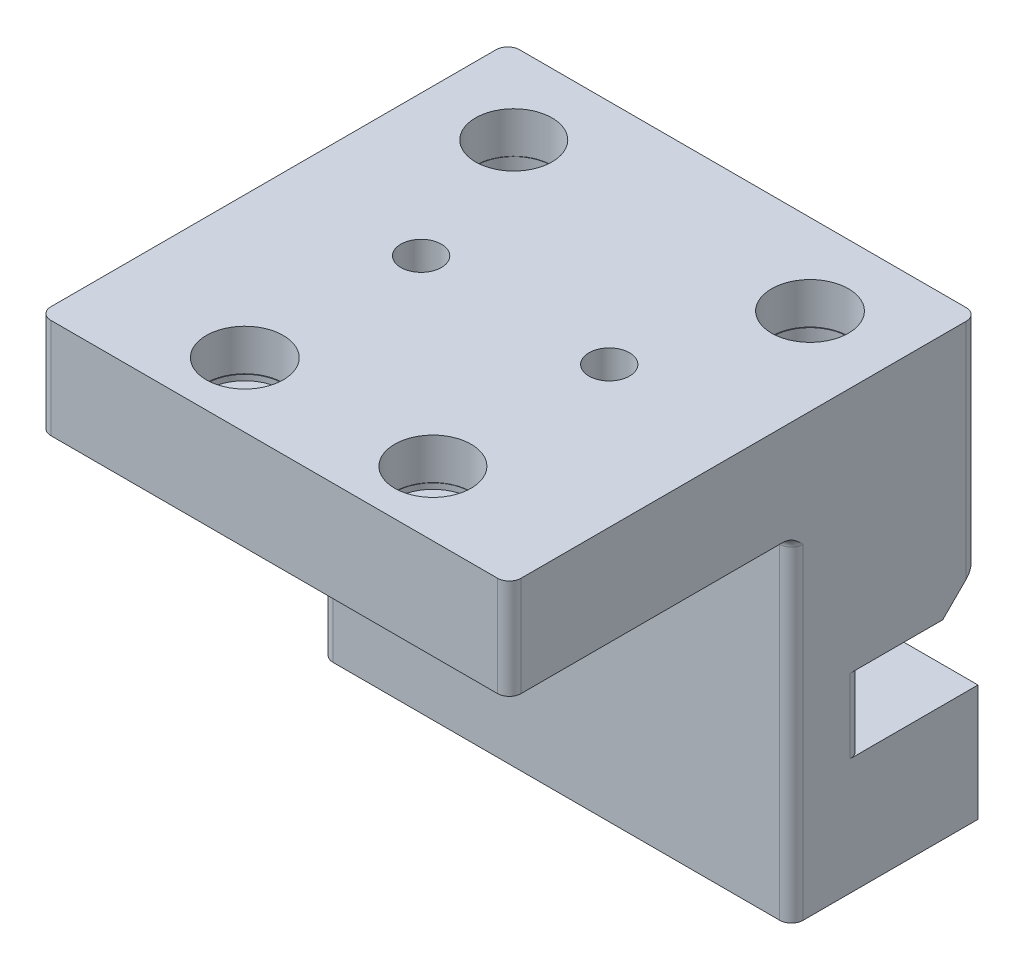
SolidWorks part; units mm, degrees
ref_plane "Front Plane" through (0, 0, 0) normal (0, 0, 1) x (1, 0, 0)
ref_plane "Top Plane" through (0, 0, 0) normal (0, 1, 0) x (1, 0, 0)
ref_plane "Right Plane" through (0, 0, 0) normal (1, 0, 0) x (0, 0, -1)
sketch "Sketch1" plane through (0, 0, 0) normal (0, 1, 0) x (1, 0, 0)
  line L1 (20, 11) -> (-20, 11)
  line L2 (20, 11) -> (20, -11)
  line L3 (20, -11) -> (-20, -11)
  line L4 (-20, 11) -> (-20, -11)
  line L5 (20, 11) -> (-20, -11) construction
  line L6 (20, -11) -> (-20, 11) construction
  point P0 (0, 0)
  dimension "D1" = 22
  dimension "D2" = 40
extrude "Boss-Extrude1" add sketch "Sketch1" along normal blind 5
sketch "Sketch2" plane through (0, 5, 0) normal (0, 1, 0) x (1, 0, 0)
  line L1 (8, 7.5) -> (-8, 7.5)
  line L2 (8, 7.5) -> (8, -7.5)
  line L3 (8, -7.5) -> (-8, -7.5)
  line L4 (-8, 7.5) -> (-8, -7.5)
  line L5 (8, 7.5) -> (-8, -7.5) construction
  line L6 (8, -7.5) -> (-8, 7.5) construction
  point P0 (0, 0)
  dimension "D1" = 15
  dimension "D2" = 16
hole_wizard "CBORE for M3 SHCS1" positions "Sketch5" profile "Sketch4" counterbore size "M3" standard "ANSI Metric" end condition through all
sketch "Sketch5" plane through (0, 5, 0) normal (0, 1, 0) x (1, 0, 0)
  point P6 (8, -7.5)
  point P9 (-8, -7.5)
sketch "Sketch4" plane through (8, 5, 7.5) normal (1, 0, 0) x (0, 0, 1)
  line L0 (0, 0) -> (0, 5)
  line L1 (0, 5) -> (1.7, 5)
  line L3 (1.7, 5) -> (1.7, 3)
  line L4 (3.25, 3) -> (1.7, 3)
  line L5 (3.25, 3) -> (3.25, 0.025)
  line L6 (3.25, 0.025) -> (3.275, 0)
  line L7 (3.275, 0) -> (0, 0)
  line L8 (-3.25, 0.025) -> (-3.275, 0) construction
  line L11 (0, -6.35) -> (0, 107.95) construction
  dimension "Thru Hole Dia." = 3.4
  dimension "Thru Hole Depth" = 5
  dimension "C'Bore Dia." = 6.5
  dimension "C'Bore Depth" = 3
  dimension "Near C'Sink Dia." = 6.55
  dimension "Near C'Sink Angle" = 90
sketch "Sketch6" plane through (0, 5, 0) normal (0, 1, 0) x (1, 0, 0)
  line L0 (20, -11) -> (20, 11) construction
  line L1 (-20, 11) -> (20, 11)
  line L2 (-20, 11) -> (-20, 17)
  line L3 (-20, 17) -> (20, 17)
  line L4 (20, 11) -> (20, 17)
  dimension "D1" = 6
extrude "Boss-Extrude2" add sketch "Sketch6" against normal blind 28.7
sketch "Sketch7" plane through (0, 0, -17) normal (0, 0, -1) x (-1, 0, 0)
  line L0 (20, -23.7) -> (20, 5) construction
  line L1 (-20, -23.7) -> (20, -23.7)
  line L2 (-20, -23.7) -> (-20, -18.8)
  line L3 (-20, -18.8) -> (20, -18.8)
  line L4 (20, -23.7) -> (20, -18.8)
  dimension "D1" = 4.9
extrude "Boss-Extrude3" add sketch "Sketch7" along normal blind 9.87
sketch "Sketch8" plane through (0, 0, -17) normal (0, 0, -1) x (-1, 0, 0)
  line L0 (20, -18.8) -> (20, 5) construction
  line L1 (-20, 5) -> (20, 5)
  line L2 (-20, 5) -> (-20, -12.5)
  line L3 (-20, -12.5) -> (20, -12.5)
  line L4 (20, 5) -> (20, -12.5)
  dimension "D1" = 17.5
extrude "Boss-Extrude4" add sketch "Sketch8" along normal up to surface (9.87 mm away) up to face at (0, -21.25, -26.87)
sketch "Sketch18" plane through (0, 0, 11) normal (0, 0, 1) x (1, 0, 0)
  line L4 (-20, 0) -> (20, 0)
  line L5 (20, 0) -> (20, 5)
  line L6 (20, 5) -> (-20, 5)
  line L7 (-20, 5) -> (-20, 0)
  line L8 (-20, 0) -> (20, 0)
  line L9 (20, 0) -> (20, 5)
  line L10 (20, 5) -> (-20, 5)
  line L11 (-20, 5) -> (-20, 0)
  dimension "D1" = 0
extrude "Boss-Extrude7" add sketch "Sketch18" along normal blind 2
sketch "Sketch9" plane through (0, 5, 0) normal (0, 1, 0) x (1, 0, 0)
  line L0 (-20, 19.98) -> (20, 19.98) construction
  line L1 (-20, 26.87) -> (-20, -13) construction
  line L2 (20, -13) -> (20, 26.87) construction
  line L3 (-12.6009, 19.98) -> (12.6009, 19.98)
  line L4 (20, 26.87) -> (-20, 26.87) construction
  point P6 (-12.6009, 19.98)
  point P7 (12.6009, 19.98)
  point P11 (0, 19.98)
  dimension "D1" = 6.89
hole_wizard "CBORE for M3 SHCS2" positions "Sketch10" profile "Sketch11" counterbore size "M3" standard "ANSI Metric" end condition through all
sketch "Sketch10" plane through (0, 5, 0) normal (0, 1, 0) x (1, 0, 0)
  point P0 (-12.6009, 19.98)
  point P3 (12.6009, 19.98)
sketch "Sketch11" plane through (-12.6009, 5, -19.98) normal (1, 0, 0) x (0, 0, 1)
  line L0 (0, 0) -> (0, 28.7)
  line L1 (0, 28.7) -> (1.7, 28.7)
  line L3 (1.7, 28.7) -> (1.7, 3)
  line L4 (3.25, 3) -> (1.7, 3)
  line L5 (3.25, 3) -> (3.25, 0.025)
  line L6 (3.25, 0.025) -> (3.275, 0)
  line L7 (3.275, 0) -> (0, 0)
  line L8 (-3.25, 0.025) -> (-3.275, 0) construction
  line L11 (0, -6.35) -> (0, 107.95) construction
  dimension "Thru Hole Dia." = 3.4
  dimension "Thru Hole Depth" = 28.7
  dimension "C'Bore Dia." = 6.5
  dimension "C'Bore Depth" = 3
  dimension "Near C'Sink Dia." = 6.55
  dimension "Near C'Sink Angle" = 90
chamfer "Chamfer1" distance 3 angle 45 1 edges at (0, -12.5, -26.87)
fillet "Fillet2" radius 1 9 edges at (-20, -11.85, -11) (20, -11.85, -11) (-20, -21.25, -26.87) (-20, -2.25, -26.87) (20, -2.25, -26.87) (-20, -15.65, -17) (20, -15.65, -17) (20, 2.5, 13) (-20, 2.5, 13)
hole_wizard "M3 Clearance Hole1" positions "Sketch14" profile "Sketch13" hole size "M3" standard "ANSI Metric" end condition through all
sketch "Sketch14" plane through (0, 5, 0) normal (0, 1, 0) x (1, 0, 0)
  point P0 (-8, 7.5)
  point P4 (8, 7.5)
sketch "Sketch13" plane through (-8, 5, -7.5) normal (1, 0, 0) x (0, 0, 1)
  line L0 (0, 0) -> (0, 28.7)
  line L1 (0, 28.7) -> (1.7, 28.7)
  line L2 (1.7, 28.7) -> (1.7, 0.025)
  line L3 (1.7, 0.025) -> (1.725, 0)
  line L5 (1.725, 0) -> (0, 0)
  line L6 (-1.7, 0.025) -> (-1.725, 0) construction
  line L11 (0, -6.35) -> (0, 107.95) construction
  dimension "Thru Hole Dia." = 3.4
  dimension "Thru Hole Depth" = 28.7
  dimension "Near C'Sink Dia." = 3.45
  dimension "Near C'Sink Angle" = 90
fillet "Fillet3" radius 1 3 edges at (19.7071, 0, -11.2929) (-19.7071, 0, -11.2929) (0, 0, -11)
sketch "Sketch15" plane through (0, -23.7, 0) normal (0, -1, 0) x (1, 0, 0)
  line L1 (15.9009, -19.98) -> (14.2509, -17.1221)
  line L2 (14.2509, -17.1221) -> (10.9509, -17.1221)
  line L3 (10.9509, -17.1221) -> (9.3009, -19.98)
  line L4 (9.3009, -19.98) -> (10.9509, -22.8379)
  line L5 (10.9509, -22.8379) -> (14.2509, -22.8379)
  line L6 (14.2509, -22.8379) -> (15.9009, -19.98)
  line L7 (-9.3009, -19.98) -> (-10.9509, -17.1221)
  line L8 (-10.9509, -17.1221) -> (-14.2509, -17.1221)
  line L9 (-14.2509, -17.1221) -> (-15.9009, -19.98)
  line L10 (-15.9009, -19.98) -> (-14.2509, -22.8379)
  line L11 (-14.2509, -22.8379) -> (-10.9509, -22.8379)
  line L12 (-10.9509, -22.8379) -> (-9.3009, -19.98)
  circle A0 centre (12.6009, -19.98) radius 2.8579 construction
  circle A1 centre (-12.6009, -19.98) radius 2.8579 construction
  dimension "D1" = 3.3
extrude "Cut-Extrude1" cut sketch "Sketch15" against normal blind 3
sketch "Sketch16" plane through (0, -23.7, 0) normal (0, -1, 0) x (1, 0, 0)
  line L0 (-15.9009, -19.98) -> (-14.2509, -22.8379) construction
  line L1 (-14.2509, -17.1221) -> (-15.9009, -19.98) construction
  line L2 (-10.9509, -17.1221) -> (-14.2509, -17.1221) construction
  line L3 (-9.3009, -19.98) -> (-10.9509, -17.1221) construction
  line L4 (19, -11) -> (-19, -11)
  line L5 (-20, -12) -> (-20, -25.87)
  line L6 (-19, -26.87) -> (20, -26.87)
  line L7 (20, -26.87) -> (20, -12)
  line L8 (19, -11) -> (-19, -11)
  line L9 (-20, -12) -> (-20, -25.87)
  line L10 (-19, -26.87) -> (20, -26.87)
  line L11 (20, -26.87) -> (20, -12)
  line L12 (-10.9509, -22.8379) -> (-9.3009, -19.98) construction
  line L14 (14.2509, -17.1221) -> (10.9509, -17.1221) construction
  line L15 (10.9509, -17.1221) -> (9.3009, -19.98) construction
  line L18 (14.2509, -22.8379) -> (15.9009, -19.98) construction
  line L19 (15.9009, -19.98) -> (14.2509, -17.1221) construction
  line L20 (10.9509, -22.8379) -> (14.2509, -22.8379) construction
  line L21 (9.3009, -19.98) -> (10.9509, -22.8379) construction
  line L22 (-14.2509, -22.8379) -> (-10.9509, -22.8379) construction
  line L23 (10.9509, -22.8379) -> (14.2509, -22.8379)
  line L24 (14.2509, -22.8379) -> (15.9009, -19.98)
  line L25 (15.9009, -19.98) -> (14.2509, -17.1221)
  line L26 (14.2509, -17.1221) -> (10.9509, -17.1221)
  line L27 (10.9509, -17.1221) -> (9.3009, -19.98)
  line L28 (9.3009, -19.98) -> (10.9509, -22.8379)
  line L29 (-10.9509, -22.8379) -> (-9.3009, -19.98)
  line L30 (-14.2509, -22.8379) -> (-10.9509, -22.8379)
  line L31 (-15.9009, -19.98) -> (-14.2509, -22.8379)
  line L32 (-14.2509, -17.1221) -> (-15.9009, -19.98)
  line L33 (-10.9509, -17.1221) -> (-14.2509, -17.1221)
  line L34 (-9.3009, -19.98) -> (-10.9509, -17.1221)
  arc A4 (-19, -11) -> (-20, -12) centre (-19, -12) ccw
  arc A5 (-20, -25.87) -> (-19, -26.87) centre (-19, -25.87) ccw
  arc A7 (20, -12) -> (19, -11) centre (19, -12) ccw
  arc A8 (-19, -11) -> (-20, -12) centre (-19, -12) ccw
  arc A9 (-20, -25.87) -> (-19, -26.87) centre (-19, -25.87) ccw
  arc A11 (20, -12) -> (19, -11) centre (19, -12) ccw
  dimension "D1" = 0
extrude "Boss-Extrude6" add sketch "Sketch16" along normal blind 5
sketch "Sketch19" plane through (0, 5, 0) normal (0, 1, 0) x (1, 0, 0)
  line L4 (-19, -13) -> (19, -13)
  line L5 (20, -12) -> (20, 25.87)
  line L6 (19, 26.87) -> (-19, 26.87)
  line L7 (-20, 25.87) -> (-20, -12)
  line L8 (-19, -13) -> (19, -13)
  line L9 (20, -12) -> (20, 25.87)
  line L10 (19, 26.87) -> (-19, 26.87)
  line L11 (-20, 25.87) -> (-20, -12)
  circle A0 centre (-12.6009, 19.98) radius 3.25 construction
  circle A1 centre (-8, 7.5) radius 1.725 construction
  circle A2 centre (8, 7.5) radius 1.725 construction
  circle A3 centre (8, -7.5) radius 3.25 construction
  arc A4 (19, -13) -> (20, -12) centre (19, -12) ccw
  arc A5 (20, 25.87) -> (19, 26.87) centre (19, 25.87) ccw
  arc A6 (-19, 26.87) -> (-20, 25.87) centre (-19, 25.87) ccw
  arc A7 (-20, -12) -> (-19, -13) centre (-19, -12) ccw
  arc A8 (19, -13) -> (20, -12) centre (19, -12) ccw
  arc A9 (20, 25.87) -> (19, 26.87) centre (19, 25.87) ccw
  arc A10 (-19, 26.87) -> (-20, 25.87) centre (-19, 25.87) ccw
  arc A11 (-20, -12) -> (-19, -13) centre (-19, -12) ccw
  circle A12 centre (-8, -7.5) radius 3.275 construction
  circle A13 centre (-8, -7.5) radius 3.275
  circle A14 centre (8, -7.5) radius 3.25
  circle A15 centre (8, 7.5) radius 1.725
  circle A16 centre (-8, 7.5) radius 1.725
  circle A17 centre (-12.6009, 19.98) radius 3.25
  circle A18 centre (12.6009, 19.98) radius 3.275 construction
  circle A19 centre (12.6009, 19.98) radius 3.275
  dimension "D1" = 0
extrude "Boss-Extrude8" add sketch "Sketch19" along normal blind 3.5
sketch "Sketch20" plane through (0, 2, 0) normal (0, 1, 0) x (1, 0, 0)
  circle A0 centre (-8, -7.5) radius 3.25 construction
  circle A1 centre (8, -7.5) radius 3.25 construction
  circle A2 centre (-8, -7.5) radius 3.25
  circle A3 centre (8, -7.5) radius 3.25
  circle A4 centre (8, -7.5) radius 1.7 construction
  circle A5 centre (-8, -7.5) radius 1.7 construction
  circle A6 centre (8, -7.5) radius 1.7
  circle A7 centre (-8, -7.5) radius 1.7
extrude "Boss-Extrude9" add sketch "Sketch20" along normal blind 2.5
